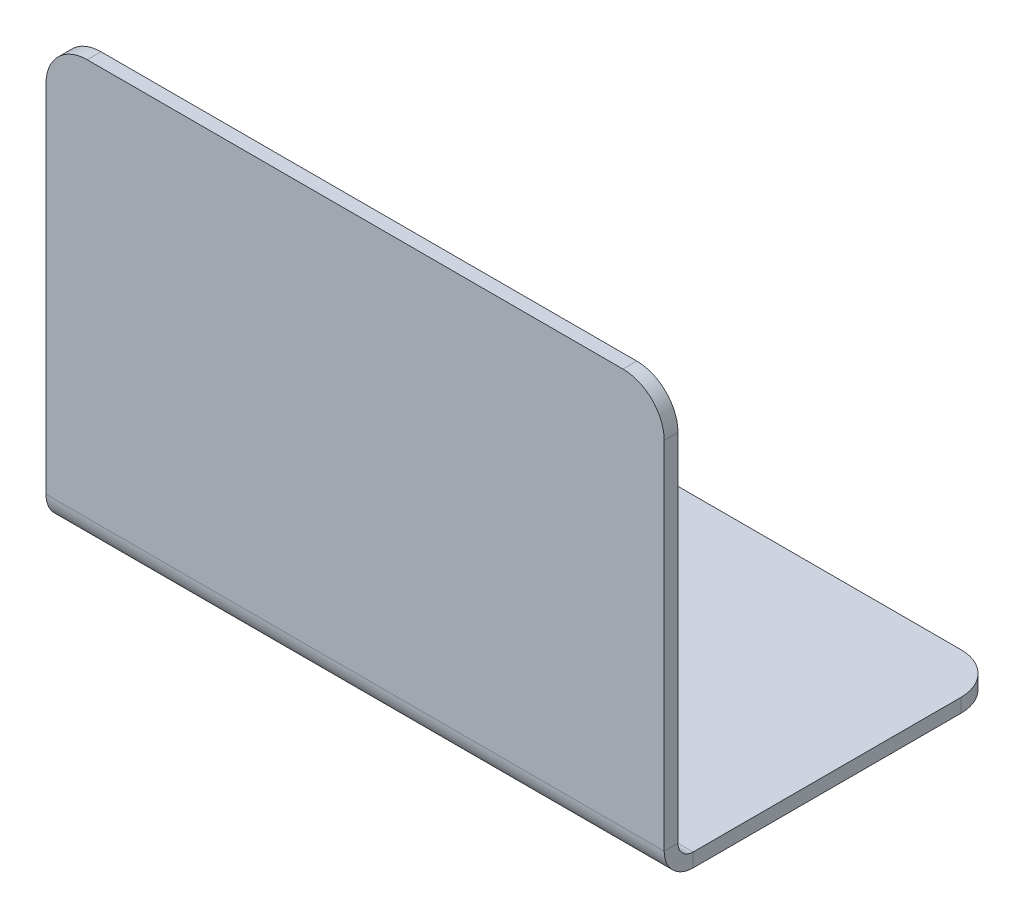
SolidWorks part; units mm, degrees
note: The reader was unsure of these and kept them because the rebuilt part matched: flange length of "Edge-Flange1".
material "6061 Alloy"
ref_plane "Front Plane" through (0, 0, 0) normal (0, 0, 1) x (1, 0, 0)
ref_plane "Top Plane" through (0, 0, 0) normal (0, 1, 0) x (1, 0, 0)
ref_plane "Right Plane" through (0, 0, 0) normal (1, 0, 0) x (0, 0, -1)
sketch "Sketch1" plane through (0, 0, 0) normal (0, 1, 0) x (1, 0, 0)
  line L1 (0, 0) -> (30, 0)
  line L2 (0, 0) -> (0, -15)
  line L3 (0, -15) -> (30, -15)
  line L4 (30, 0) -> (30, -15)
  dimension "D1" = 30
  dimension "D2" = 15
sheet metal parameters "Sheet-Metal1" thickness 0.67 parameters "D1"=0.7366
base flange "Base-Flange1" sketch "Sketch1" thickness 0.67 reverse thickness direction no parameters "D1"=0.7366
edge flange "Edge-Flange1" sketch "Sketch6" flange angle 90 flange length 20 flange position bend outside bend radius 0.7366 thickness 0.67 relief rectangular parameters "D6"=10
sketch "Sketch6" plane through (0, 0, 15) normal (0, 0, 1) x (1, 0, 0)
  line L0 (0, 0) -> (30, 0) construction
  line L1 (0, 0) -> (30, 0)
  line L2 (0, 0) -> (0, 20)
  line L3 (0, 20) -> (30, 20)
  line L4 (30, 20) -> (30, 0)
  dimension "D1" = 20
bend "EdgeBend1" bend radius 0.7366 bend angle 90 parameters "D5"=1
sketch "Sketch7" plane through (0, 0, 0) normal (0, 1, 0) x (1, 0, 0)
  line L2 (15, 0) -> (15, -15) construction
  line L3 (30, 0) -> (0, 0) construction
  line L4 (0, -15) -> (30, -15) construction
  circle A0 centre (15, -7.9066) radius 1.7
  dimension "D4" = 3.4
  dimension "D1" = 8.5
extrude "Cut-Extrude1" cut sketch "Sketch7" against normal blind 10 normal cut yes
fillet "Fillet1" radius 2 4 edges at (0, -0.335, 0) (30, -0.335, 0) (0, 20, 16.0716) (30, 20, 16.0716)
flat pattern "Flat-Pattern1" [suppressed]
sketch "Bend-Lines1" plane through (0, 0, 0) normal (0, 1, 0) x (1, 0, 0)
  line L0 (0, -15.8416) -> (30, -15.8416) construction
  line L1 (0, -15.8416) -> (30, -15.8416) construction
sketch3d "Bounding-Box1" [suppressed]
  line L0 (30, 0, 0) -> (30, -35.9467, 0) construction
  line L1 (0, 0, 0) -> (0, -35.9466, 0) construction
  line L2 (30, 0, 0) -> (0, 0, 0) construction
  line L3 (30, -35.9467, 0) -> (0, -35.9466, 0) construction
bend of the flat pattern "Flatten-<EdgeBend1>1"
